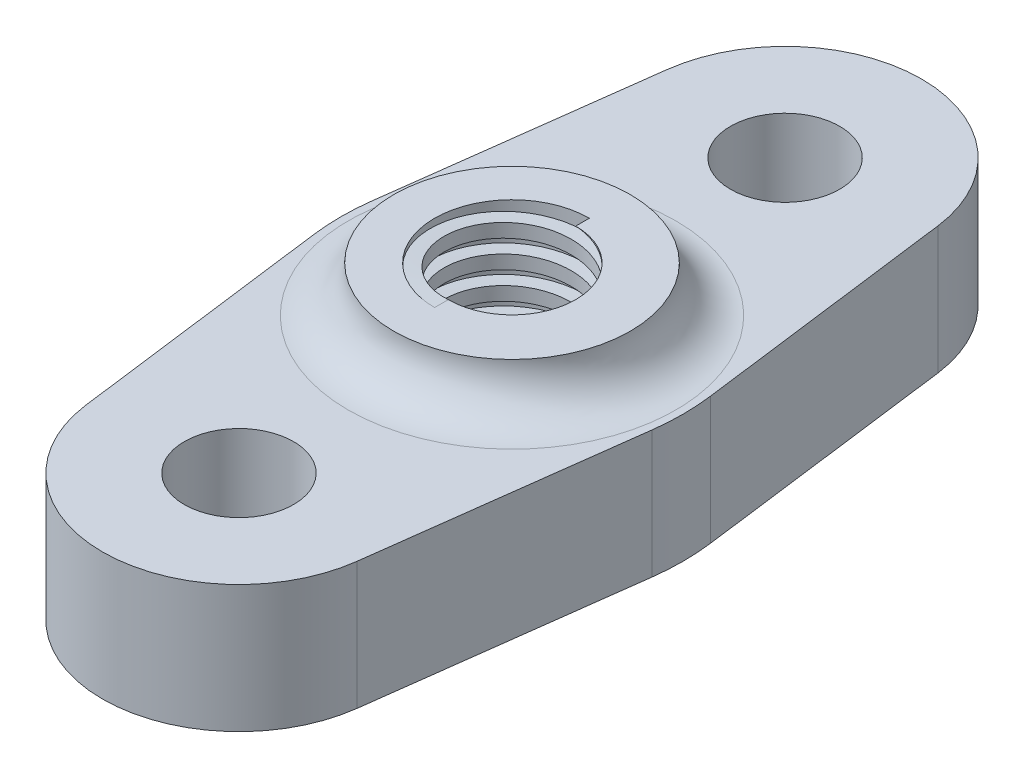
SolidWorks part; units mm, degrees
ref_plane "Front Plane" through (0, 0, 0) normal (0, 0, 1) x (1, 0, 0)
ref_plane "Top Plane" through (0, 0, 0) normal (0, 1, 0) x (1, 0, 0)
ref_plane "Right Plane" through (0, 0, 0) normal (1, 0, 0) x (0, 0, -1)
sketch "Sketch1" plane through (0, 0, 0) normal (1, 0, 0) x (0, 0, -1)
  line L0 (0, 32.0585) -> (0, -22.8654) construction
  line L1 (-60.3313, 0) -> (68.4524, 0) construction
  line L2 (14, 0) -> (90, 0)
  line L3 (90, 0) -> (90, 28)
  line L4 (90, 28) -> (36, 28)
  line L5 (26, 38) -> (14, 38)
  line L6 (14, 38) -> (14, 0)
  arc A0 (36, 28) -> (26, 38) centre (36, 38) cw
  point P11 (34.7757, 36.8506)
  point P13 (0, 0)
  dimension "D1" = 14
  dimension "D2" = 26
  dimension "D3" = 90
  dimension "D4" = 10
  dimension "D5" = 28
revolve "Revolve1" add sketch "Sketch1" angle 360 about L0
sketch "Sketch2" plane through (0, 28, 0) normal (0, 1, 0) x (1, 0, 0)
  line L0 (0, 73.0728) -> (0, -70.3058) construction
  line L1 (-74.8336, 0) -> (76.8459, 0) construction
  line L2 (-29.7528, 63.8434) -> (-38, 0)
  line L3 (29.7528, 63.8434) -> (38, 0)
  line L4 (29.7528, -63.8434) -> (38, 0)
  line L5 (-29.7528, -63.8434) -> (-38, 0)
  circle A0 centre (0, 60) radius 30
  circle A1 centre (0, 60) radius 12
  circle A2 centre (0, -60) radius 12
  circle A3 centre (0, -60) radius 30
  circle M8 centre (0, 0) radius 90
  dimension "D1" = 60
  dimension "D2" = 24
  dimension "D3" = 120
  dimension "D4" = 76
extrude "Cut-Extrude1" cut sketch "Sketch2" against normal through all and the other way through all contours L4 A3 A0 L3 M8 | A3 L5 L2 A0 M8 | A2 | A1
fillet "Fillet1" radius 50 2 edges at (-38, 14, 0) (38, 14, 0)
sketch "Sketch3" plane through (0, 38, 0) normal (0, 1, 0) x (1, 0, 0)
  circle A0 centre (0, 0) radius 17
  dimension "D1" = 34
curve "Helix/Spiral1" pitch 6 height 50 turns 8.3333
sketch "Sketch4" plane through (0, 0, 0) normal (1, 0, 0) x (0, 0, -1)
  line L1 (-17, 41) -> (-14, 41)
  line L2 (-17, 41) -> (-17, 38)
  line L3 (-17, 38) -> (-14, 38)
  line L4 (-14, 41) -> (-14, 38)
  line L5 (-17, 41) -> (-14, 38) construction
  line L6 (-17, 38) -> (-14, 41) construction
  point P0 (-15.5, 39.5)
  point P5 (0, 0)
  dimension "D1" = 3
  dimension "D2" = 3
sweep "Cut-Sweep1" cut profiles "Sketch4" path "Helix/Spiral1"
